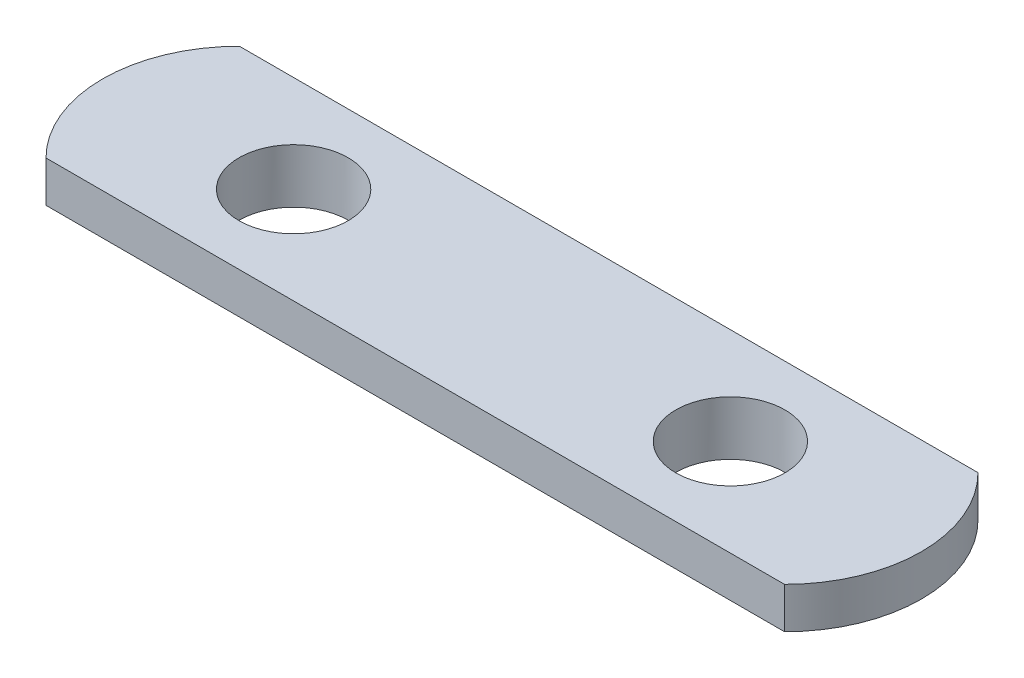
SolidWorks part; units mm, degrees
ref_plane "Front Plane" through (0, 0, 0) normal (0, 0, 1) x (1, 0, 0)
ref_plane "Top Plane" through (0, 0, 0) normal (0, 1, 0) x (1, 0, 0)
ref_plane "Right Plane" through (0, 0, 0) normal (1, 0, 0) x (0, 0, -1)
sketch "Sketch1" plane through (0, 0, 0) normal (0, 1, 0) x (1, 0, 0)
  line L0 (-12.7, 0) -> (12.7, 0) construction
  circle A0 centre (-12.7, 0) radius 3.175
  point P3 (-15.875, 0)
  point P4 (-9.525, 0)
  dimension "D1" = 6.35
  dimension "D2" = 25.4
extrude "Boss-Extrude1" add sketch "Sketch1" against normal blind 12.7
sketch "Sketch2" plane through (0, -12.7, 0) normal (0, -1, 0) x (1, 0, 0)
  circle A1 centre (-12.7, 0) radius 3.175
  circle A2 centre (-12.7, 0) radius 3.175
  point P0 (-12.7, -3.175)
  dimension "D1" = 0
curve "Helix/Spiral1" pitch 1.27 height 13.97 turns 11
ref_plane "Plane1" through (-12.7, 0, 0) normal (1, 0, 0) x (0, 0, -1)
sketch "Sketch3" plane through (-12.7, 0, 0) normal (1, 0, 0) x (0, 0, -1)
  line L0 (3.3125, -12.6206) -> (2.2126, -13.2556) construction
  line L1 (2.2126, -13.2556) -> (3.3125, -13.8906) construction
  line L2 (3.3125, -13.8906) -> (3.3125, -12.6206) construction
  line L3 (2.3501, -13.1762) -> (2.3501, -13.335) construction
  line L4 (3.175, -12.7) -> (3.175, -13.8112) construction
  line L5 (2.2126, -13.2556) -> (2.3501, -13.2556) construction
  line L6 (3.175, -13.2556) -> (3.3125, -13.2556) construction
  line L8 (2.2126, -13.2556) -> (-3.175, -13.2556) construction
  line L9 (2.3501, -13.1762) -> (3.2437, -12.6603)
  line L10 (2.3501, -13.1762) -> (2.3501, -13.335)
  line L11 (2.3501, -13.335) -> (3.2437, -13.8509)
  line L12 (3.2437, -13.8509) -> (3.2437, -12.6603)
  line L14 (-3.175, -13.2556) -> (-3.175, -11.9856) construction
  line L15 (-3.175, -11.9856) -> (-3.175, -10.7156) construction
  line L16 (-3.175, -10.7156) -> (-3.175, -9.4456) construction
  line L17 (-3.175, -9.4456) -> (-3.175, -8.1756) construction
  line L18 (-3.175, 0) -> (-3.175, -12.7) construction
  point P15 (3.2437, -13.2556)
  dimension "D1" = 1.27
  dimension "D2" = 0.1588
sweep "Cut-Sweep1" cut profiles "Sketch3" path "Helix/Spiral1"
sketch "Sketch4" plane through (0, -12.7, 0) normal (0, -1, 0) x (1, 0, 0)
  circle A0 centre (-12.7, 0) radius 2.2126
extrude "Cut-Extrude1" cut sketch "Sketch4" against normal blind 1.27 draft 45 flip side to cut
sketch "Sketch5" plane through (0, 0, 0) normal (0, 0, 1) x (1, 0, 0)
  line L0 (-12.7, 0) -> (-12.7, 3.3528)
  line L1 (-19.6342, 0) -> (-12.7, 0)
  line L2 (-12.7, 3.3528) -> (-15.875, 3.3528)
  line L3 (-18.2499, 0.8382) -> (-19.6342, 0.8382)
  line L4 (-19.6342, 0.8382) -> (-19.6342, 0)
  line L5 (-12.7, 0) -> (-12.7, -12.7) construction
  arc A0 (-15.875, 3.3528) -> (-18.2499, 0.8382) centre (-12.7, -2.0246) ccw
  dimension "D1" = 3.3528
  dimension "D2" = 0.8382
  dimension "D3" = 13.8684
  dimension "D4" = 11.0998
revolve "Revolve1" add sketch "Sketch5" angle 360 mid plane about L0
sketch "Sketch6" plane through (0, 3.3528, 0) normal (0, 1, 0) x (1, 0, 0)
  line L1 (-12.7, 2.2914) -> (-14.6844, 1.1457)
  line L2 (-14.6844, 1.1457) -> (-14.6844, -1.1457)
  line L3 (-14.6844, -1.1457) -> (-12.7, -2.2914)
  line L4 (-12.7, -2.2914) -> (-10.7156, -1.1457)
  line L5 (-10.7156, -1.1457) -> (-10.7156, 1.1457)
  line L6 (-10.7156, 1.1457) -> (-12.7, 2.2914)
  circle A0 centre (-12.7, 0) radius 1.9844 construction
  dimension "D1" = 3.9688
extrude "Cut-Extrude2" cut sketch "Sketch6" against normal blind 2.3813
sketch "Sketch7" plane through (0, 3.3528, 0) normal (0, 1, 0) x (1, 0, 0)
  circle A0 centre (-12.7, 0) radius 2.2914
extrude "Cut-Extrude3" cut sketch "Sketch7" against normal blind 2.3813 draft 45
move or copy body "Body-Move/Copy1" bodies to move or copy 110 copy yes number of copies 1 translate (25.4, 0, 0)
sketch "Sketch8" plane through (0, 0, 0) normal (0, 1, 0) x (1, 0, 0)
  line L0 (-23.8125, 0) -> (23.8125, 0) construction
  line L1 (-21.4742, 5.6261) -> (21.4742, 5.6261)
  line L2 (-21.4742, -5.6261) -> (21.4742, -5.6261)
  line L4 (-23.8125, 5.6261) -> (23.8125, 5.6261) construction
  line L5 (-23.8125, 5.6261) -> (-23.8125, -5.6261) construction
  line L6 (-23.8125, -5.6261) -> (23.8125, -5.6261) construction
  line L7 (23.8125, 5.6261) -> (23.8125, -5.6261) construction
  arc A0 (-21.4742, 5.6261) -> (-21.4742, -5.6261) centre (-15.875, 0) ccw
  arc A1 (21.4742, 5.6261) -> (21.4742, -5.6261) centre (15.875, 0) cw
  circle A3 centre (-12.7, 0) radius 3.175
  circle A4 centre (-12.7, 0) radius 3.175
  circle A5 centre (12.7, 0) radius 3.175
  dimension "D2" = 47.625
  dimension "D4" = 7.9375
  dimension "D3" = 11.2522
  dimension "D1" = 0
extrude "Boss-Extrude2" add sketch "Sketch8" against normal blind 2.3876 from offset 6.35 separate body offset against normal yes
sketch "Sketch9" plane through (0, -8.7376, 0) normal (0, -1, 0) x (1, 0, 0)
  circle A0 centre (12.7, 0) radius 3.175
  circle A1 centre (-12.7, 0) radius 3.175 construction
  circle A2 centre (-12.7, 0) radius 3.175
  circle A3 centre (-12.7, 0) radius 3.5687
  circle A4 centre (12.7, 0) radius 3.5687
  dimension "D1" = 7.1374
extrude "Boss-Extrude3" add sketch "Sketch9" along normal blind 0.762
sketch "SketchZ" plane through (0, 0, 0) normal (0, 0, 1) x (1, 0, 0)
  line L0 (-9.525, -12.9381) -> (-9.525, -11.6681) construction
  line L2 (-12.7, -13.2556) -> (-12.7, -11.9856) construction
  line L4 (-9.525, -12.9381) -> (-12.7, -12.9381) construction
  line L5 (-12.7, -9.4456) -> (-12.7, -8.1756) construction
  line L6 (-12.7, -12.6206) -> (-12.7, -13.2556) construction
delete or keep bodies "Body-Delete/Keep 1" type delete bodies bodies 110
delete or keep bodies "Body-Delete/Keep 2" type delete bodies bodies 136
equation "\"D3@Helix/Spiral1\" = \"D4@Helix/Spiral1\" + \"D1@Boss-Extrude1\""
equation "\"D1@Sketch3\" = \"D4@Helix/Spiral1\""
equation "\"D2@Sketch3\" = \"D1@Sketch3\" / 8"
equation "\"D1@Cut-Extrude1\" = \"D4@Helix/Spiral1\""
equation "\"D1@Cut-Extrude2\" = \"D1@Sketch6\" * 3/5"
equation "\"D1@Cut-Extrude3\" = \"D1@Cut-Extrude2\""
equation "\"D2@Sketch5\" = \"D1@Sketch5\" * 1/4"
